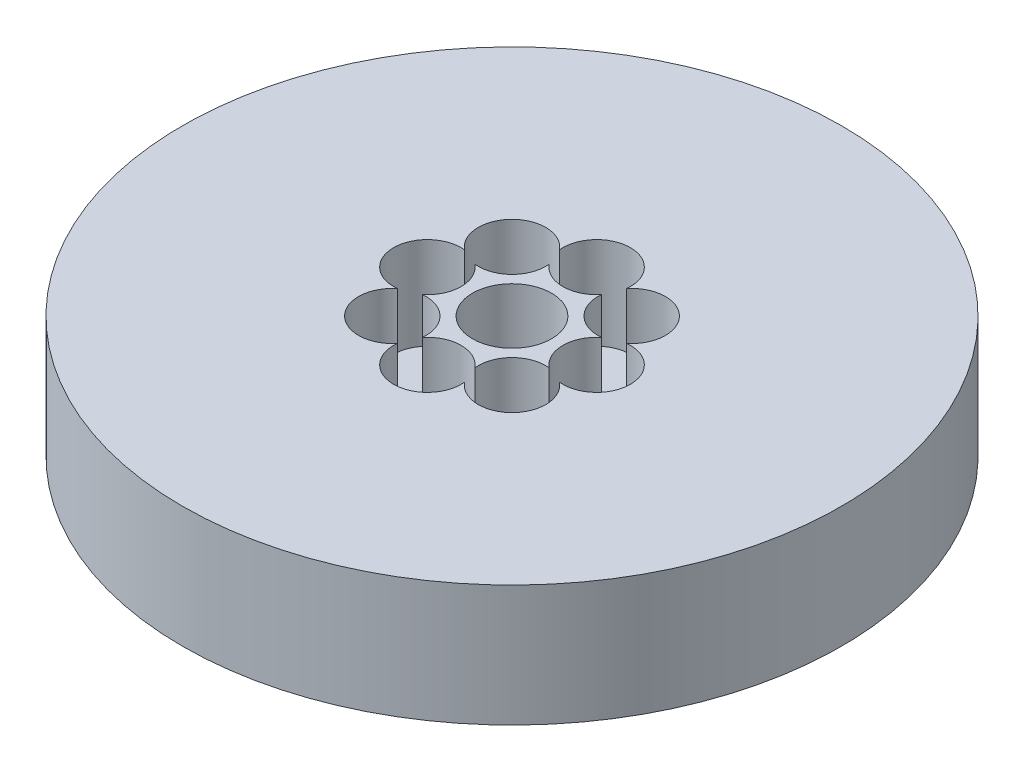
SolidWorks part; units mm, degrees
ref_plane "Front Plane" through (0, 0, 0) normal (0, 0, 1) x (1, 0, 0)
ref_plane "Top Plane" through (0, 0, 0) normal (0, 1, 0) x (1, 0, 0)
ref_plane "Right Plane" through (0, 0, 0) normal (1, 0, 0) x (0, 0, -1)
sketch "Sketch1" plane through (0, 0, 0) normal (0, 1, 0) x (1, 0, 0)
  circle A0 centre (0, 0) radius 62.5
  dimension "FLANGE_OD" = 125
extrude "Boss-Extrude1" add sketch "Sketch1" along normal blind 23
sketch "Sketch2" plane through (0, 0, 0) normal (0, 1, 0) x (1, 0, 0)
  circle A0 centre (0, 0) radius 7.5
  dimension "BORE_D" = 15
extrude "Cut-Extrude1" cut sketch "Sketch2" along normal through all
sketch "Sketch3" plane through (0, 23, 0) normal (0, 1, 0) x (1, 0, 0)
  circle A0 centre (0, 0) radius 16.0513 construction
  circle A1 centre (-16.0513, 0) radius 6.4023
  dimension "BOLT_D" = 12.8046
  dimension "BOLT_PCD" = 32.1026
extrude "Cut-Extrude2" cut sketch "Sketch3" against normal blind 17.5188
pattern_circular "CirPattern1" count 8 over 360 about axis through (0, 0, 0) along (0, 1, 0) of "Cut-Extrude2"
